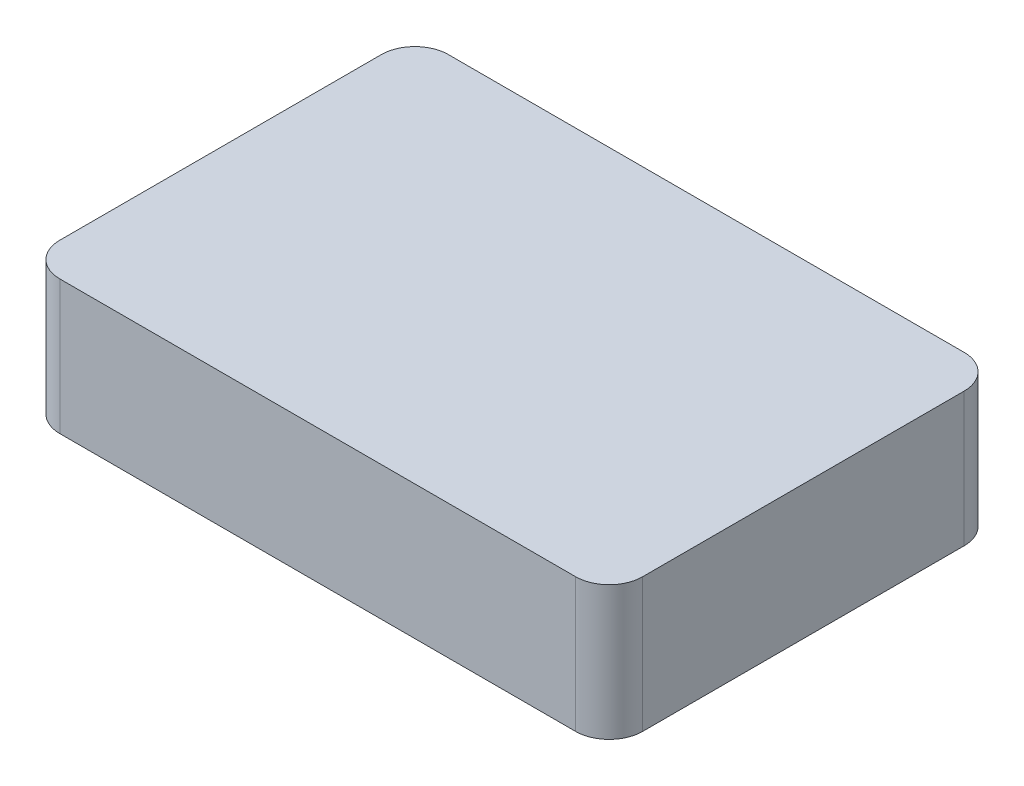
SolidWorks part; units mm, degrees
ref_plane "Alzado" through (0, 0, 0) normal (0, 0, 1) x (1, 0, 0)
ref_plane "Planta" through (0, 0, 0) normal (0, 1, 0) x (1, 0, 0)
ref_plane "Vista lateral" through (0, 0, 0) normal (1, 0, 0) x (0, 0, -1)
sketch "Croquis1" plane through (0, 0, 0) normal (0, 1, 0) x (1, 0, 0)
  line L1 (43.5, -29) -> (-43.5, -29)
  line L2 (43.5, -29) -> (43.5, 29)
  line L3 (43.5, 29) -> (-43.5, 29)
  line L4 (-43.5, -29) -> (-43.5, 29)
  line L5 (43.5, -29) -> (-43.5, 29) construction
  line L6 (43.5, 29) -> (-43.5, -29) construction
  point P0 (0, 0)
  dimension "D1" = 87
  dimension "D2" = 58
extrude "Saliente-Extruir1" add sketch "Croquis1" along normal blind 20
fillet "Redondeo1" radius 5 4 edges at (-43.5, 10, -29) (43.5, 10, -29) (-43.5, 10, 29) (43.5, 10, 29)
